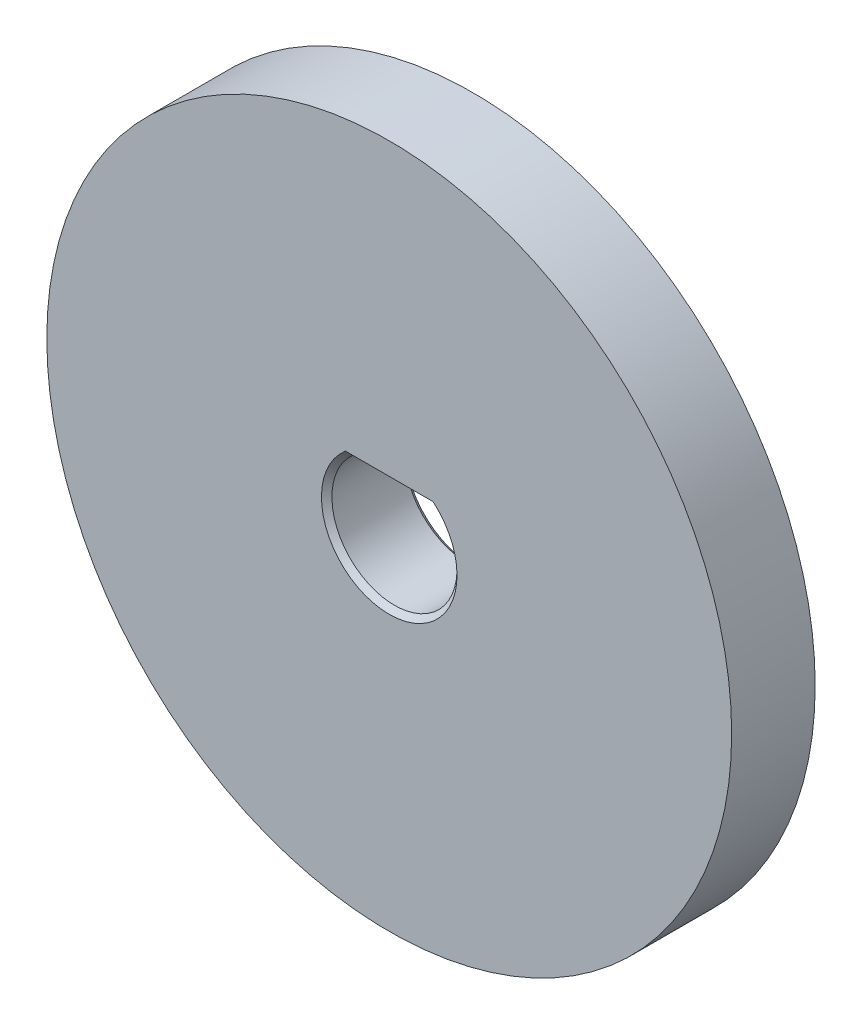
SolidWorks part; units mm, degrees
material "6061-T6 (SS)"
ref_plane "Front Plane" through (0, 0, 0) normal (0, 0, 1) x (1, 0, 0)
ref_plane "Top Plane" through (0, 0, 0) normal (0, 1, 0) x (1, 0, 0)
ref_plane "Right Plane" through (0, 0, 0) normal (1, 0, 0) x (0, 0, -1)
sketch "Sketch1" plane through (0, 0, 0) normal (0, 0, 1) x (1, 0, 0)
  circle A0 centre (0, 0) radius 52.07
  circle A1 centre (0, 0) radius 9.5123
  dimension "D1" = 104.14
  dimension "D2" = 19.0246
extrude "Extrude1" add sketch "Sketch1" along normal mid plane 12.7
sketch "Sketch2" plane through (0, 0, 0) normal (1, 0, 0) x (0, 0, -1)
  line L0 (-4.7625, 47.625) -> (4.7625, 47.625)
  line L2 (4.7625, 47.625) -> (2.4513, 41.275)
  line L3 (2.4513, 41.275) -> (-2.4513, 41.275)
  line L4 (-2.4513, 41.275) -> (-4.7625, 47.625)
  line L5 (-6.35, 0) -> (6.35, 0) construction
  line L6 (-6.35, 52.07) -> (-6.35, -52.07) construction
  line L7 (6.35, -52.07) -> (6.35, 52.07) construction
  point P2 (0, 47.625)
  point P5 (0, 41.275)
  dimension "D1" = 47.625
  dimension "D2" = 6.35
  dimension "D3" = 9.525
  dimension "D4" = 40
sketch "Sketch3" plane through (0, 0, -6.35) normal (0, 0, -1) x (-1, 0, 0)
  line L0 (-6.3595, 7.0739) -> (6.3595, 7.0739)
  line L1 (0, 7.0739) -> (0, -9.5123) construction
  circle A0 centre (0, 0) radius 9.5123 construction
  circle A2 centre (0, 0) radius 9.5123
  arc A3 (6.3595, 7.0739) -> (-6.3595, 7.0739) centre (0, 0) ccw
  dimension "D1" = 16.5862
  dimension "D2" = 0
extrude "Boss-Extrude1" add sketch "Sketch3" against normal up to surface (12.7 mm away) up to face at (52.07, 0, 6.35)
chamfer "Chamfer3" distance 0.795 angle 45 4 edges at (0, -9.5123, 6.35) (0, 7.0739, 6.35) (0, 7.0739, -6.35) (0, -9.5123, -6.35)
